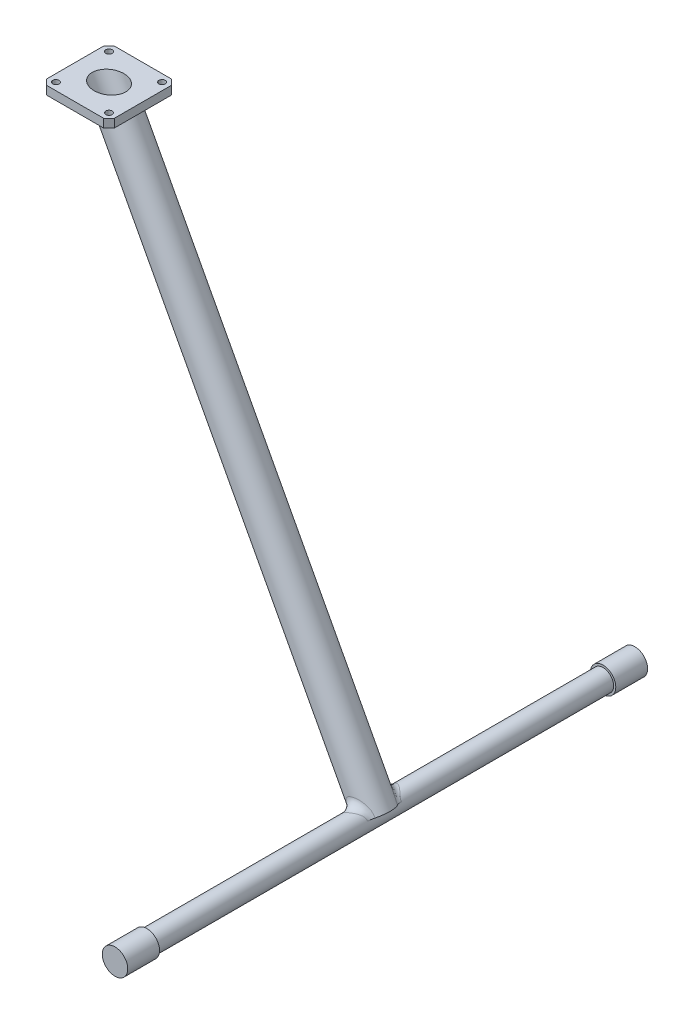
SolidWorks part; units mm, degrees
note: The reader was unsure of these and kept them because the rebuilt part matched: shared geometry of "Sketch3<2>", "Sketch3<3>", "Sketch5<2>".
material "Thornel VCB-20 Carbon Cloth"
ref_plane "Front Plane" through (0, 0, 0) normal (0, 0, 1) x (1, 0, 0)
ref_plane "Top Plane" through (0, 0, 0) normal (0, 1, 0) x (1, 0, 0)
ref_plane "Right Plane" through (0, 0, 0) normal (1, 0, 0) x (0, 0, -1)
sketch "Sketch1" plane through (0, 0, 0) normal (0, 1, 0) x (1, 0, 0)
  line L0 (-12.5, 12.5) -> (12.5, 12.5) construction
  line L1 (12.5, 12.5) -> (12.5, -12.5) construction
  line L2 (12.5, -12.5) -> (-12.5, -12.5) construction
  line L3 (-12.5, -12.5) -> (-12.5, 12.5) construction
  line L4 (-16, 16) -> (-16, -16)
  line L5 (-16, -16) -> (16, -16)
  line L6 (16, -16) -> (16, 16)
  line L7 (16, 16) -> (-16, 16)
  circle A0 centre (-12.5, 12.5) radius 1.5
  circle A1 centre (12.5, 12.5) radius 1.5
  circle A2 centre (12.5, -12.5) radius 1.5
  circle A3 centre (-12.5, -12.5) radius 1.5
  point P8 (0, 12.5)
  point P9 (12.5, 0)
  point P15 (0, 16)
  point P16 (16, 0)
  dimension "D1" = 3
  dimension "D2" = 25
  dimension "D3" = 25
  dimension "D4" = 32
extrude "Boss-Extrude1" add sketch "Sketch1" against normal blind 4
chamfer "Chamfer1" distance 2.5 angle 45 4 edges at (-16, -2, -16) (16, -2, -16) (16, -2, 16) (-16, -2, 16)
sketch "Sketch2" plane through (0, 0, 0) normal (0, 0, 1) x (1, 0, 0)
  line L0 (0, 0) -> (0, -240) construction
  line L2 (0, -240) -> (128, -240) construction
  line L3 (128, -240) -> (0, 0) construction
  dimension "D1" = 272
  dimension "D2" = 240
ref_plane "Plane1" through (128, -240, 0) normal (-0.4706, 0.8824, 0) x (0.8824, 0.4706, 0)
sketch "Sketch3" plane through (128, -240, 0) normal (-0.4706, 0.8824, 0) x (0.8824, 0.4706, 0)
  circle A0 centre (0, 0) radius 7
  circle A1 centre (0, 0) radius 8
  dimension "D1" = 16
  dimension "D2" = 14
extrude "Boss-Extrude2" add sketch "Sketch3" along normal up to next
extrude "Cut-Extrude1" cut sketch "Sketch3<2>" along normal up to next contours A0
sketch "Sketch3<2>" plane through (128, -240, 0) normal (-0.4706, 0.8824, 0) x (0.8824, 0.4706, 0) same geometry as "Sketch3"
extrude "Cut-Extrude2" cut sketch "Sketch3<3>" along normal blind 5.5
sketch "Sketch3<3>" plane through (128, -240, 0) normal (-0.4706, 0.8824, 0) x (0.8824, 0.4706, 0) same geometry as "Sketch3"
sketch "Sketch5" plane through (0, 0, 0) normal (0, 0, 1) x (1, 0, 0)
  line L0 (0, -240) -> (128, -240) construction
  line L1 (128, -240) -> (0, 0) construction
  circle A0 centre (125.3333, -235) radius 5
  circle A1 centre (125.3333, -235) radius 4
  dimension "D1" = 10
  dimension "D2" = 8
extrude "Boss-Extrude3" add sketch "Sketch5" along normal blind 122.5 and the other way blind 122.5
extrude "Cut-Extrude3" cut sketch "Sketch5<2>" against normal through all both and the other way through all contours A1
sketch "Sketch5<2>" plane through (0, 0, 0) normal (0, 0, 1) x (1, 0, 0) same geometry as "Sketch5"
fillet "Fillet1" radius 4 2 edges at (122.5221, -230.8651, 7.9821) (122.6299, -230.7939, -7.9897)
sketch "Sketch6" plane through (0, 0, 122.5) normal (0, 0, 1) x (1, 0, 0)
  circle A0 centre (125.3333, -235) radius 5 construction
  circle A1 centre (125.3333, -235) radius 5 construction
  circle A2 centre (125.3333, -235) radius 6
  dimension "D1" = 12
extrude "Boss-Extrude4" add sketch "Sketch6" against normal blind 15
mirror "Mirror1" about plane through (0, 0, 0) normal (0, 0, 1) of "Boss-Extrude4"
